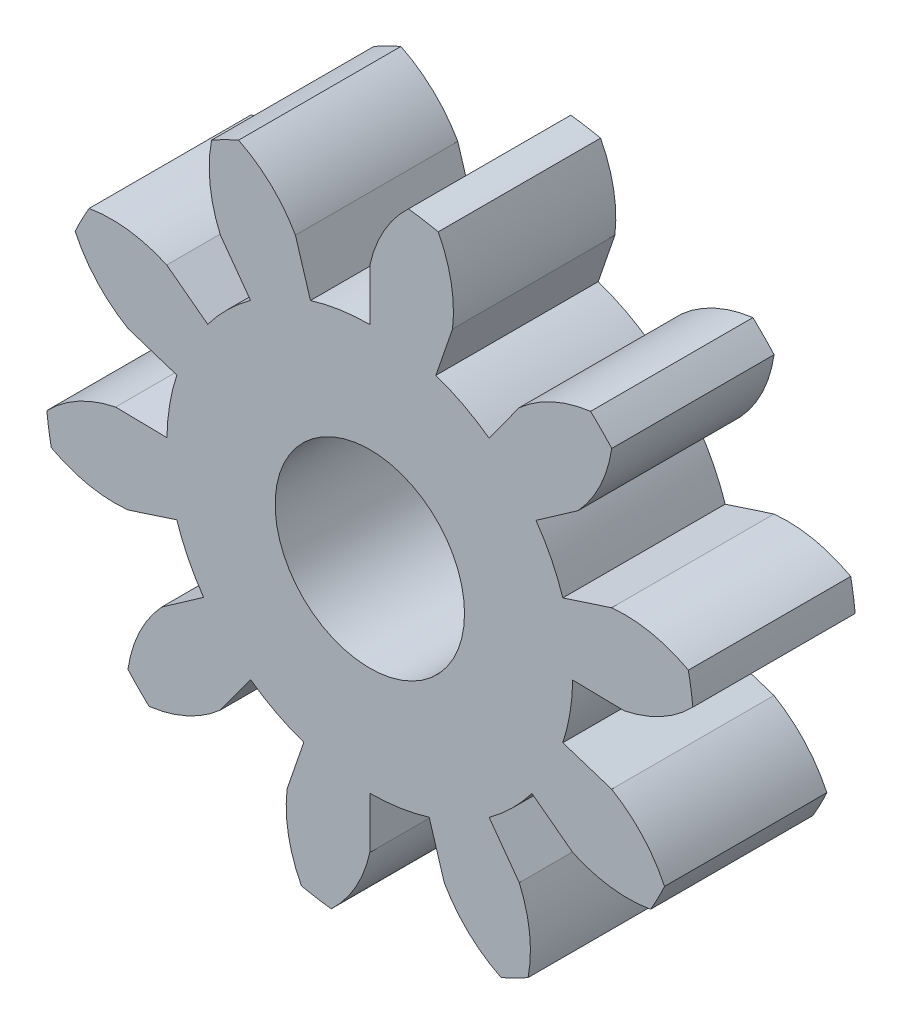
SolidWorks part; units mm, degrees
ref_plane "Plan de face" through (0, 0, 0) normal (0, 0, 1) x (1, 0, 0)
ref_plane "Plan de dessus" through (0, 0, 0) normal (0, 1, 0) x (1, 0, 0)
ref_plane "Plan de droite" through (0, 0, 0) normal (1, 0, 0) x (0, 0, -1)
sketch "Esquisse1" plane through (0, 0, 0) normal (0, 0, 1) x (1, 0, 0)
  circle A0 centre (0, 0) radius 5
  circle A1 centre (0, 0) radius 6
  circle A2 centre (0, 0) radius 3.75
  circle A3 centre (0, 0) radius 4
  circle A4 centre (0, 0) radius 4.6985
  dimension "Pitch Circle" = 10
  dimension "Addendum Circle" = 12
  dimension "Root Circle" = 7.5
  dimension "Clearence Circle" = 8
  dimension "Base Circle" = 9.3969
sketch "Involute" plane through (0, 0, 0) normal (0, 0, 1) x (1, 0, 0)
  line L0 (0, 0) -> (0, 4.6985)
  line L1 (0, 0) -> (2.3492, 4.069) construction
  line L2 (0, 0) -> (4.069, 2.3492) construction
  line L3 (0, 0) -> (4.6985, 0) construction
  line L4 (4.6985, 0) -> (4.6985, 7.3803) construction
  line L5 (4.069, 2.3492) -> (1.6089, 6.6103) construction
  line L6 (2.3492, 4.069) -> (0.2187, 5.299) construction
  line L7 (0, 0) -> (1.5451, 4.7553) construction
  line L8 (2.9389, 4.0451) -> (0, 0)
  line L9 (0.8247, 4.9315) -> (0, 0) construction
  circle A0 centre (0, 0) radius 4.6985 construction
  circle A1 centre (0, 0) radius 5 construction
  arc A2 (1.5451, 4.7553) -> (0.0861, 4.9993) centre (0, 0) ccw
  spline S0 degree 3 poles (0, 4.6985) (0.4133, 6.6226) (3.1129, 7.3828) (4.6985, 7.3803) knots 0 0 0 0 1 1 1 1
  spline S1 degree 3 poles (1.5287, 4.4428) (1.7639, 6.3967) (-0.5415, 7.994) (-2.0416, 8.5074) knots 0 0 0 0 1 1 1 1
  dimension "Involute Control" = 90
  dimension "Base Circle Quarter Circumference" = 7.3803
  dimension "D1" = 4.9202
  dimension "D2" = 2.4601
  dimension "Circular Pitch" = 36
  dimension "Involute Array" = 4
sketch "Esquisse4" plane through (0, 0, 0) normal (0, 0, 1) x (1, 0, 0)
  line L0 (0, 0) -> (0, 4.6985) construction
  line L1 (0, 4.6985) -> (0, 3.75)
  line L2 (1.5287, 4.4428) -> (1.2201, 3.546)
  arc A0 (0.7133, 5.9575) -> (1.2638, 5.8654) centre (0, 0) cw
  circle A1 centre (0, 0) radius 6 construction
  arc A2 (0, 3.75) -> (1.2201, 3.546) centre (0, 0) cw
  circle A3 centre (0, 0) radius 3.75 construction
  arc A4 (0, 4.6985) -> (0.7133, 5.9575) centre (2.387, 4.1776) cw
  arc A5 (1.2638, 5.8654) -> (1.5287, 4.4428) centre (-0.898, 4.727) cw
  spline S0 degree 3 poles (0, 4.6985) (0.4133, 6.6226) (3.1129, 7.3828) (4.6985, 7.3803) knots 0 0 0 0 1 1 1 1 construction
  spline S1 degree 3 poles (1.5287, 4.4428) (1.7639, 6.3967) (-0.5415, 7.994) (-2.0416, 8.5074) knots 0 0 0 0 1 1 1 1 construction
extrude "Boss.-Extru.1" add sketch "Esquisse4" along normal blind 3
ref_axis "Axe1" through (0, 0, 0) along (0, 0, 1)
pattern_circular "Répétition circulaire2" count 10 over 360 about axis through (0, 0, 0) along (0, 0, 1) of bodies 101
sketch "Esquisse5" plane through (0, 0, 0) normal (0, 0, 1) x (1, 0, 0)
  circle A0 centre (0, 0) radius 3.75 construction
  circle A1 centre (0, 0) radius 3.75
extrude "Boss.-Extru.2" add sketch "Esquisse5" along normal up to surface (3 mm away) up to face at (-4.2558, 2.2148, 3)
sketch "Esquisse6" plane through (0, 0, 3) normal (0, 0, 1) x (1, 0, 0)
  circle A0 centre (0, 0) radius 1.75
  dimension "D1" = 3.5
extrude "Enlèv. mat.-Extru.1" cut sketch "Esquisse6" against normal through all
equation "\"Module\"= 1"
equation "\"Nb de dents\"= 10"
equation "\"Pressure Angle\"= 20"
equation "\"Pitch Circle@Esquisse1\"= \"Module\" * \"Nb de dents\""
equation "\"Addendum Circle@Esquisse1\"= \"Pitch Circle@Esquisse1\" + ( \"Module\" * 2 )"
equation "\"Clearence Circle@Esquisse1\"= \"Pitch Circle@Esquisse1\" - ( \"Module\" * 2 )"
equation "\"Root Circle@Esquisse1\"= \"Pitch Circle@Esquisse1\" - ( ( \"Module\" * 1.25 ) * 2 )"
equation "\"Base Circle@Esquisse1\"= \"Pitch Circle@Esquisse1\" * cos ( \"Pressure Angle\" )"
equation "\"Base Circle Quarter Circumference@Involute\" = \"Base Circle@Esquisse1\" * pI / 4"
equation "\"D1@Involute\"=\"Base Circle Quarter Circumference@Involute\"/3*2"
equation "\"D2@Involute\"=\"Base Circle Quarter Circumference@Involute\"/3"
equation "\"Circular Pitch@Involute\"=360/\"Nb de dents\""
equation "\"D1@Répétition circulaire2\"= \"Nb de dents\""
